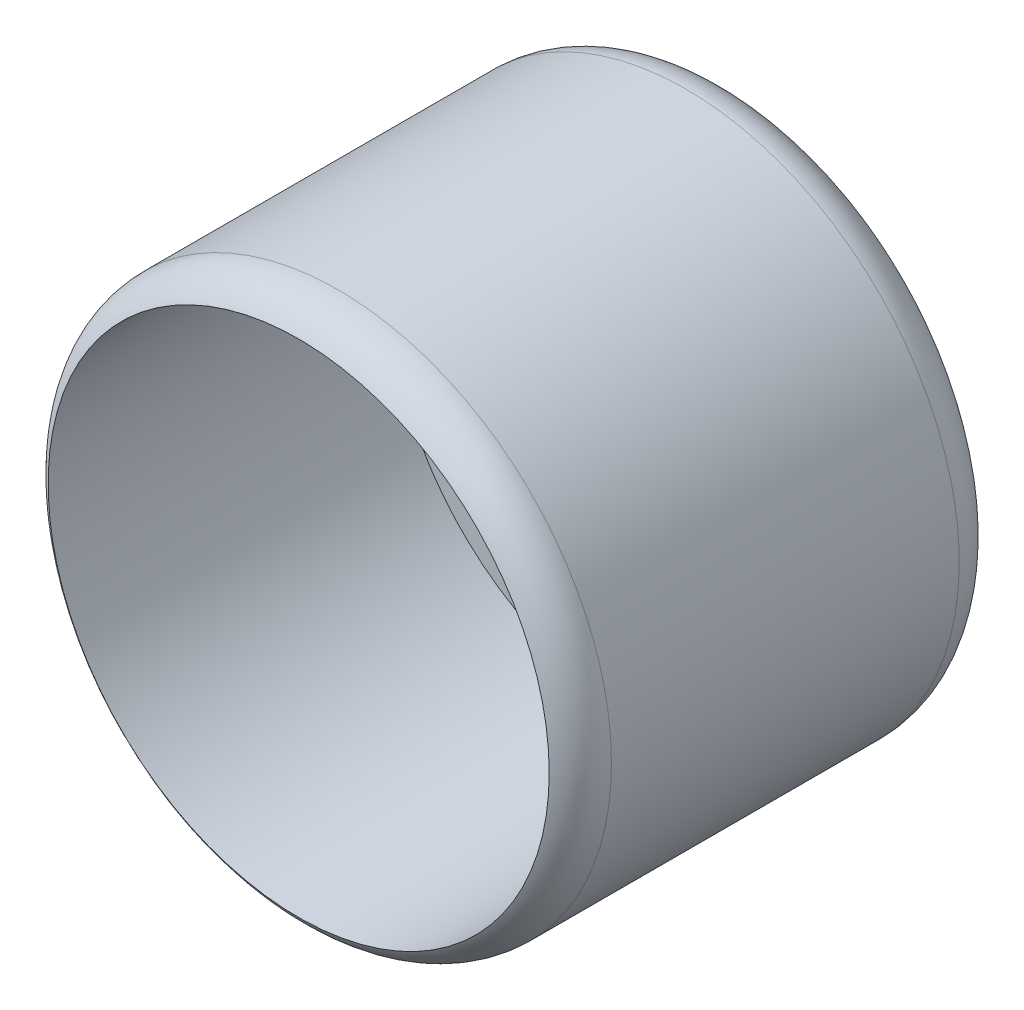
SolidWorks part; units mm, degrees
ref_plane "Plan de face" through (0, 0, 0) normal (0, 0, 1) x (1, 0, 0)
ref_plane "Plan de dessus" through (0, 0, 0) normal (0, 1, 0) x (1, 0, 0)
ref_plane "Plan de droite" through (0, 0, 0) normal (1, 0, 0) x (0, 0, -1)
sketch "Esquisse1" plane through (0, 0, 0) normal (0, 0, 1) x (1, 0, 0)
  circle A0 centre (0, 0) radius 60
  dimension "D1" = 120
extrude "Boss.-Extru.1" add sketch "Esquisse1" along normal blind 80 from offset 50 offset against normal yes
shell "Coque1" thickness 5 removed face at (60, 0, 30)
sketch "Esquisse2" plane through (0, 0, -50) normal (0, 0, -1) x (-1, 0, 0)
  circle A0 centre (0, 0) radius 60
extrude "Boss.-Extru.2" add sketch "Esquisse2" along normal blind 15
sketch "Esquisse3" plane through (0, 0, -65) normal (0, 0, -1) x (-1, 0, 0)
  circle A0 centre (0, 0) radius 17.5
  dimension "D1" = 35
extrude "Enlèv. mat.-Extru.1" cut sketch "Esquisse3" against normal up to surface (20 mm away) up to face at (55, 0, -45)
sketch "Esquisse4" plane through (0, 0, -45) normal (0, 0, 1) x (1, 0, 0)
  circle A0 centre (0, 0) radius 20
  dimension "D1" = 40
extrude "Enlèv. mat.-Extru.2" cut sketch "Esquisse4" against normal blind 1
fillet "Congé1" radius 10 1 edges at (-60, 0, -65)
fillet "Congé2" radius 10 1 edges at (60, 0, 30)
scale "Echelle1" scale about centroid uniform scaling yes scale factor 0.25
